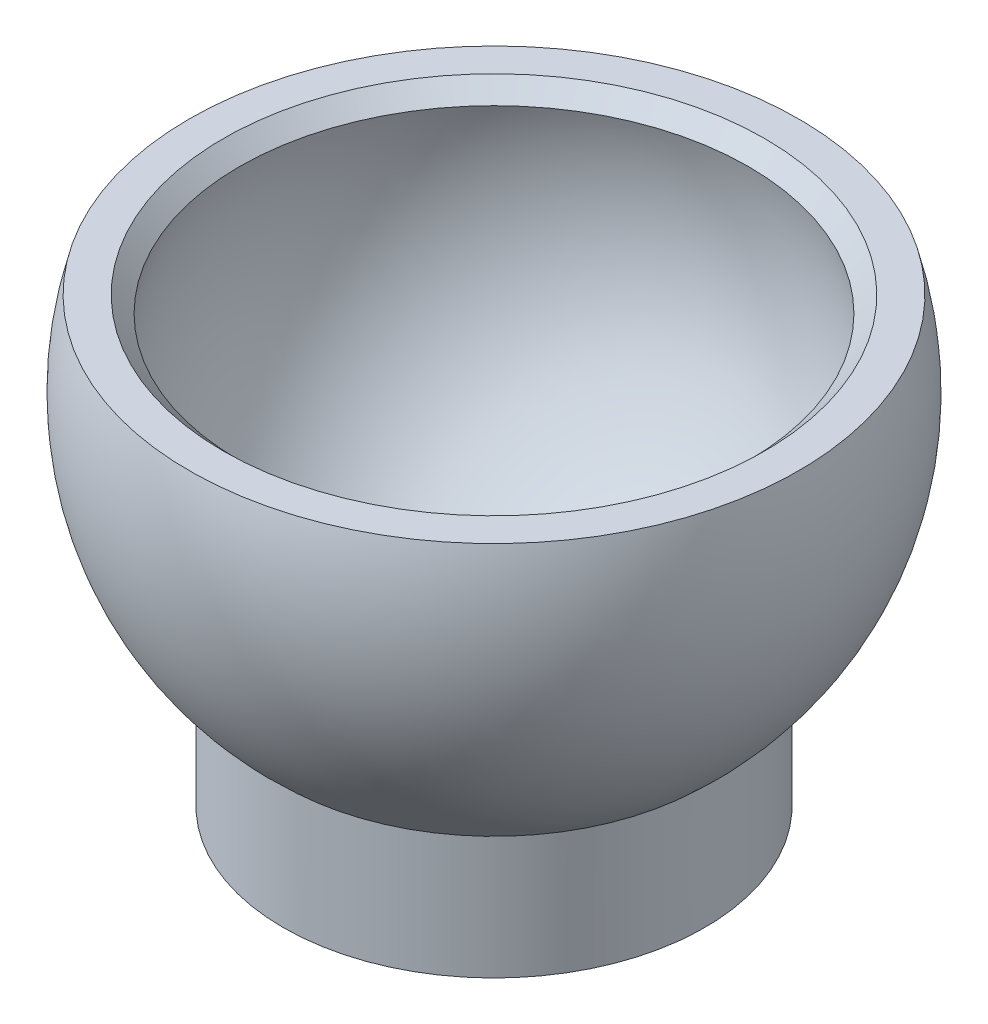
SolidWorks part; units mm, degrees
ref_plane "Front" through (0, 0, 0) normal (0, 0, 1) x (1, 0, 0)
ref_plane "Top" through (0, 0, 0) normal (0, 1, 0) x (1, 0, 0)
ref_plane "Right" through (0, 0, 0) normal (1, 0, 0) x (0, 0, -1)
sketch "Sketch1" plane through (0, 0, 0) normal (0, 0, 1) x (1, 0, 0)
  line L0 (0, 23.9947) -> (0, -26.3657) construction
  line L1 (11.8427, 4) -> (14.4568, 4)
  line L2 (0, -12.5) -> (0, -15)
  arc A0 (0, -15) -> (14.4568, 4) centre (0, 0) ccw
  arc A1 (0, -12.5) -> (11.8427, 4) centre (0, 0) ccw
  dimension "D1" = 12.5
  dimension "D2" = 15
  dimension "D3" = 4
revolve "Revolve1" add sketch "Sketch1" angle 360 about L0
sketch "Sketch2" plane through (0, 0, 0) normal (0, 1, 0) x (1, 0, 0)
  circle A0 centre (0, 0) radius 10
  dimension "D1" = 20
extrude "Boss-Extrude1" add sketch "Sketch2" along normal up to surface (5.8197 mm away) from offset 17 up to face at (0, 4, 14.4568) offset against normal yes
chamfer "Chamfer1" distance 1 angle 45 1 edges at (0, 4, 11.8427) first distance on face at (0, 4, 11.8427)
